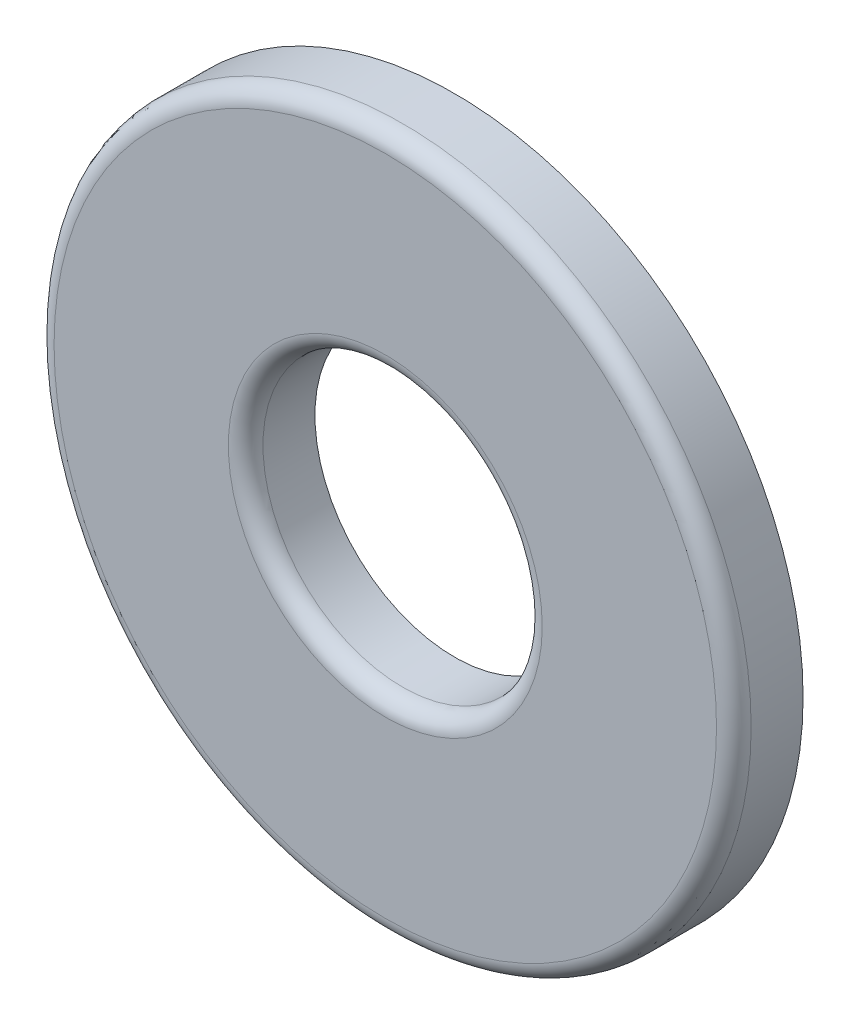
SolidWorks part; units mm, degrees
note: '?' marks a value the reader was unsure of.
other "Imported1" parameters "D1"=0.1968, "TH"=1.0287, "Thickness"=0.7874
ref_plane "Front Plane" through (0, 0, 0) normal (0, 0, 1) x (1, 0, 0)
ref_plane "Top Plane" through (0, 0, 0) normal (0, 1, 0) x (1, 0, 0)
ref_plane "Right Plane" through (0, 0, 0) normal (1, 0, 0) x (0, 0, -1)
sketch "Sketch1" plane through (0, 0, 0) normal (0, 0, 1) x (1, 0, 0)
  line L0 (-3.9624, 0) -> (3.9624, 0) construction
  line L1 (-1.5875, 0) -> (1.5875, 0) construction
  circle A0 centre (0, 0) radius 1.5875 construction
  circle A1 centre (0, 0) radius 3.9624 construction
  point P8 (0, 0)
  point P9 (0, 3.9624)
  point P11 (1.5875, 0)
  dimension "ID" = 3.175
  dimension "OD" = 7.9248
sketch "Sketch2" plane through (0, 0, 0) normal (1, 0, 0) x (0, 0, -1)
  line L0 (-0.3937, 3.9624) -> (0.3937, 3.9624) construction
  point P2 (0, 3.9624)
sketch "Sketch3" plane through (0, 0, 0) normal (0, 0, 1) x (1, 0, 0)
  circle A0 centre (0, 0) radius 1.5875
  circle A1 centre (0, 0) radius 3.9624
extrude "Boss-Extrude1" add sketch "Sketch3" along normal up to vertex (0.3937 mm away) and the other way up to vertex (0.3937 mm away) up to point (0, 3.9624, 0.3937) other way up to point (0, 3.9624, -0.3937)
fillet "Fillet1" radius 0.1968 2 edges at (3.9624, 0, 0.3937) (1.5875, 0, 0.3937)
ref_axis "Center Axis 1" through (0, 0, 0.1968) along (0, 0, -1)?
equation "\"D1@Fillet1\"=\"Thickness@Sketch2\"/4"
